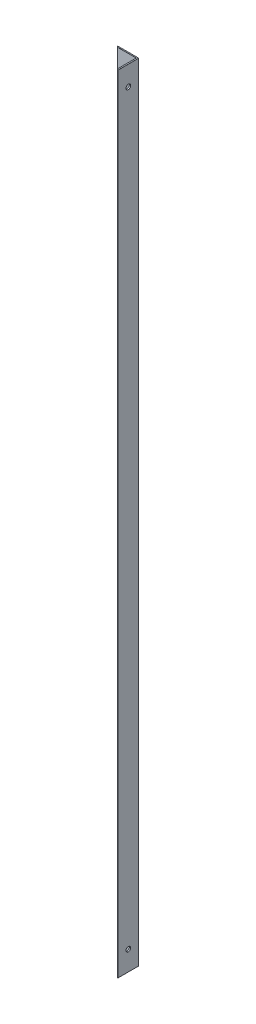
SolidWorks part; units mm, degrees
ref_plane "前视基准面" through (0, 0, 0) normal (0, 0, 1) x (1, 0, 0)
ref_plane "上视基准面" through (0, 0, 0) normal (0, 1, 0) x (1, 0, 0)
ref_plane "右视基准面" through (0, 0, 0) normal (1, 0, 0) x (0, 0, -1)
sketch "草图1" plane through (0, 0, 0) normal (0, 1, 0) x (1, 0, 0)
  line L0 (-26.9808, 0) -> (20.2405, 0)
  line L1 (20.2405, 0) -> (20.2405, -46.5554)
  line L3 (23.6851, -50) -> (23.6851, 3)
  line L4 (23.6851, 3) -> (-29.7595, 3)
  arc A0 (-29.7595, 3) -> (-26.5207, 0) centre (-26.7507, 3) ccw
  arc A1 (23.6851, -50) -> (20.2405, -46.5554) centre (23.6851, -46.5554) cw
extrude "凸台-拉伸1" add sketch "草图1" along normal blind 2000 contours A1 L3 L4 A0 L0 L1 region at (-28.4059, 0, -1.4669)
fillet "圆角1" radius 0.1 10 edges at (21.2494, 0, 48.9911) (21.2494, 2000, 48.9911) (20.2405, 0, 23.2777) (23.6851, 0, 23.5) (-3.0372, 0, -3) (-3.3702, 0, 0) (20.2405, 2000, 23.2777) (23.6851, 2000, 23.5) (-3.0372, 2000, -3) (-3.3702, 2000, 0)
sketch "草图2" plane through (23.6851, 0, 0) normal (1, 0, 0) x (0, 0, -1)
  line L0 (-23.5, 1999.9) -> (-23.5, 0.1) construction
  line L1 (3, 1999.9) -> (-50, 1999.9) construction
  line L2 (-50, 0.1) -> (3, 0.1) construction
  circle A0 centre (-23.5, 50.1) radius 6
  circle A1 centre (-23.5, 1949.9) radius 6
  point P6 (-23.5, 50.1)
  point P7 (-23.5, 1949.9)
  dimension "D3" = 12
  dimension "D4" = 12
  dimension "D1" = 50
  dimension "D2" = 50
extrude "切除-拉伸1" cut sketch "草图2" against normal blind 200
sketch "草图3" plane through (23.6851, 0, 0) normal (1, 0, 0) x (0, 0, -1)
  line L0 (-23.5, 0.1) -> (-23.5, 84.1845)
  line L1 (-50, 0.1) -> (3, 0.1) construction
  point P4 (-23.5, 50.1)
ref_plane "基准面1" through (23.6851, 50.1, 23.5) normal (0, 1, 0) x (-1, 0, 0)
sketch "草图5" plane through (0, 0, -3) normal (0, 0, -1) x (-1, 0, 0)
  line L0 (0, 0) -> (0, 128.2167)
  circle A0 centre (0, 50) radius 6
  point P3 (0, 50)
  dimension "D2" = 12
  dimension "D1" = 50
extrude "切除-拉伸2" cut sketch "草图5" against normal blind 200 contours A0
pattern_linear "阵列(线性)1" count 2 spacing 1900 along (0, 1, 0) of "切除-拉伸2"
